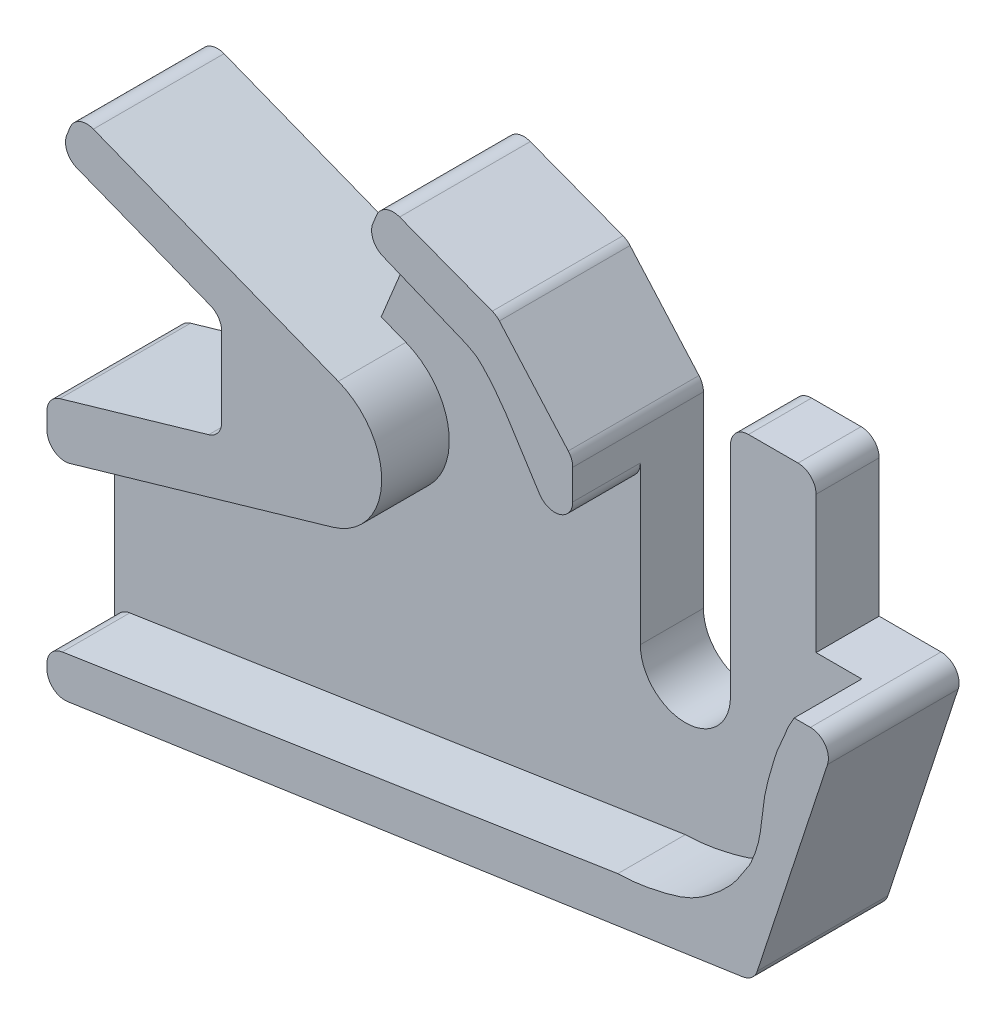
SolidWorks part; units mm, degrees
ref_plane "Front Plane" through (0, 0, 0) normal (0, 0, 1) x (1, 0, 0)
ref_plane "Top Plane" through (0, 0, 0) normal (0, 1, 0) x (1, 0, 0)
ref_plane "Right Plane" through (0, 0, 0) normal (1, 0, 0) x (0, 0, -1)
sketch "Sketch1" plane through (0, 0, 0) normal (0, 0, 1) x (1, 0, 0)
  line L0 (169.0465, 531.5792) -> (1384.9618, 942.3347) construction
  line L1 (17.1755, 0.269) -> (145.8355, -18.3486) construction
  line L2 (78.9683, 43.5936) -> (88.9683, 43.5936)
  line L3 (88.9683, 43.5936) -> (88.9683, 26.5936)
  line L4 (88.9683, 26.5936) -> (78.9683, 26.5936)
  line L5 (78.9683, 26.5936) -> (78.9683, 43.5936)
  line L6 (77.9414, 43.8024) -> (71.5407, 53.8656)
  line L7 (56.0381, 62.9033) -> (67.1668, 58.333)
  line L8 (88.9683, 43.5936) -> (88.9683, 57.7987)
  line L9 (88.9683, 57.7987) -> (98.4683, 57.7987)
  line L10 (77.9414, 43.8024) -> (78.9683, 42.1878)
  line L11 (20.6229, 24.1202) -> (53.1029, 33.5417)
  line L12 (23.9133, 59.0209) -> (55.1963, 46.7648)
  line L13 (56.0381, 62.9033) -> (50.2123, 48.7174)
  line L14 (40.0198, 9.0575) -> (20.6228, 6.0624)
  line L15 (20.6228, 6.1399) -> (20.6229, 24.1202)
  line L16 (20.6229, 24.1202) -> (20.6229, 30.1202)
  line L17 (83.9683, 15.8436) -> (40.0198, 9.0575)
  line L18 (20.6229, 30.1202) -> (43.6301, 36.7939)
  line L19 (23.9133, 59.0209) -> (22.0894, 54.3655)
  line L20 (22.0894, 54.3655) -> (44.4958, 45.587)
  line L21 (78.9683, 43.5936) -> (78.9683, 49.2858)
  line L22 (57.9376, 67.5285) -> (70.5008, 62.7543)
  line L23 (68.2195, 57.2049) -> (70.5008, 62.7543)
  line L24 (40.0198, 35.7467) -> (40.0198, 47.3406)
  line L25 (77.3776, 54.951) -> (70.5008, 62.7543)
  line L26 (56.0381, 62.9033) -> (57.9376, 67.5285)
  line L27 (103.0983, 40.5847) -> (108.0983, 40.5847)
  line L28 (103.3884, 40.3163) -> (103.5353, 40.5847)
  line L29 (108.0983, 40.5847) -> (99.0557, 13.0352)
  line L30 (98.4683, 57.7987) -> (98.4683, 40.5847)
  line L31 (99.0557, 13.0352) -> (20.6228, 1.5127)
  line L32 (20.6228, 1.5127) -> (20.6228, 6.1399)
  line L38 (78.9683, 49.2858) -> (78.9683, 52.8143)
  line L39 (77.3776, 54.951) -> (78.9683, 53.146)
  line L46 (78.9683, 53.146) -> (78.9683, 52.8143)
  line L47 (98.4683, 40.5847) -> (103.0983, 40.5847)
  line L50 (83.9683, 26.5936) -> (83.9683, 15.8436) construction
  circle A0 centre (83.9683, 31.5936) radius 5
  circle A1 centre (83.9683, 38.5936) radius 5
  circle A5 centre (50.1903, 40.5872) radius 7.578
  spline S0 degree 3 poles (67.1668, 58.333) (67.5307, 58.1482) (68.2163, 57.8297) (69.7375, 56.3376) (70.7671, 54.998) (71.5407, 53.8656) knots 0 0 0 0 0.194176 0.353383 1 1 1 1
  spline S1 degree 3 poles (83.9683, 15.8436) (85.8004, 15.8611) (88.1737, 16.2893) (90.9758, 17.071) (92.712, 17.8244) (94.4321, 19.053) (96.0427, 20.4541) (97.1642, 21.7522) (97.8521, 22.923) (98.5915, 23.8956) (99.0767, 25.0782) (99.6537, 26.7034) (99.9224, 28.6807) (100.1457, 30.8488) (100.5189, 32.8624) (101.1101, 34.6453) (101.5072, 36.2279) (102.0659, 37.4006) (102.4863, 38.4066) (102.8484, 39.4294) (103.2109, 39.9904) (103.3884, 40.3163) knots 0 0 0 0 0.157855 0.207039 0.251095 0.320551 0.388512 0.43536 0.467801 0.505699 0.540278 0.577572 0.654532 0.711417 0.766137 0.830869 0.873613 0.906585 0.94275 0.967881 1 1 1 1
  dimension "D1" = 130
  dimension "D2" = 10
  dimension "D3" = 17
  dimension "D4" = 9.5
  dimension "D10" = 10.75
extrude "Boss-Extrude1" add sketch "Sketch1" along normal blind 7 contours L17 S1 L28 L27 L47 L30 L9 L8 L3 L4 L5 L10 L6 S0 L7 L13 L12 A5 L11 L15 | A0 L4 L3 | A0 L5 L4 region at (63.2298, 30.1191, 0) region at (87.8514, 27.7104, 0) region at (80.0851, 27.7104, 0)
extrude "Boss-Extrude2" add sketch "Sketch1<3>" along normal blind 14.5 contours A5 L12 L19 L20 | A5 | A5 L20 L24 L18 | A5 L18 L16 L11 | S1 L17 L32 L31 L29 L27 L28 | L23 S0 L6 L10 L5 L21 L38 L46 L39 L25 | L7 S0 L23 L22 L26 region at (74.5437, 53.5182, 0) region at (63.3137, 62.7114, 0) region at (105.8168, 39.6267, 0) region at (35.1841, 52.0124, 0) region at (50.1903, 40.5872, 0) region at (41.5617, 41.668, 0) region at (33.5189, 30.7275, 0)
sketch "Sketch1<3>" plane through (0, 0, 0) normal (0, 0, 1) x (1, 0, 0) same geometry as "Sketch1"
fillet "Fillet1" radius 2 17 edges at (78.9683, 53.146, 7.25) (70.5008, 62.7543, 7.25) (99.0557, 13.0352, 7.25) (108.0983, 40.5847, 7.25) (98.4683, 57.7987, 3.5) (88.9683, 57.7987, 3.5) (57.9376, 67.5285, 7.25) (56.0381, 62.9033, 10.75) (78.9683, 42.1878, 10.75) (20.6228, 1.5127, 7.25) (20.6229, 24.1202, 10.75) (20.6229, 30.1202, 7.25) (23.9133, 59.0209, 7.25) (22.0894, 54.3655, 7.25) (40.0198, 47.3406, 7.25) (40.0198, 35.7467, 7.25) (20.6228, 6.0624, 10.75)
